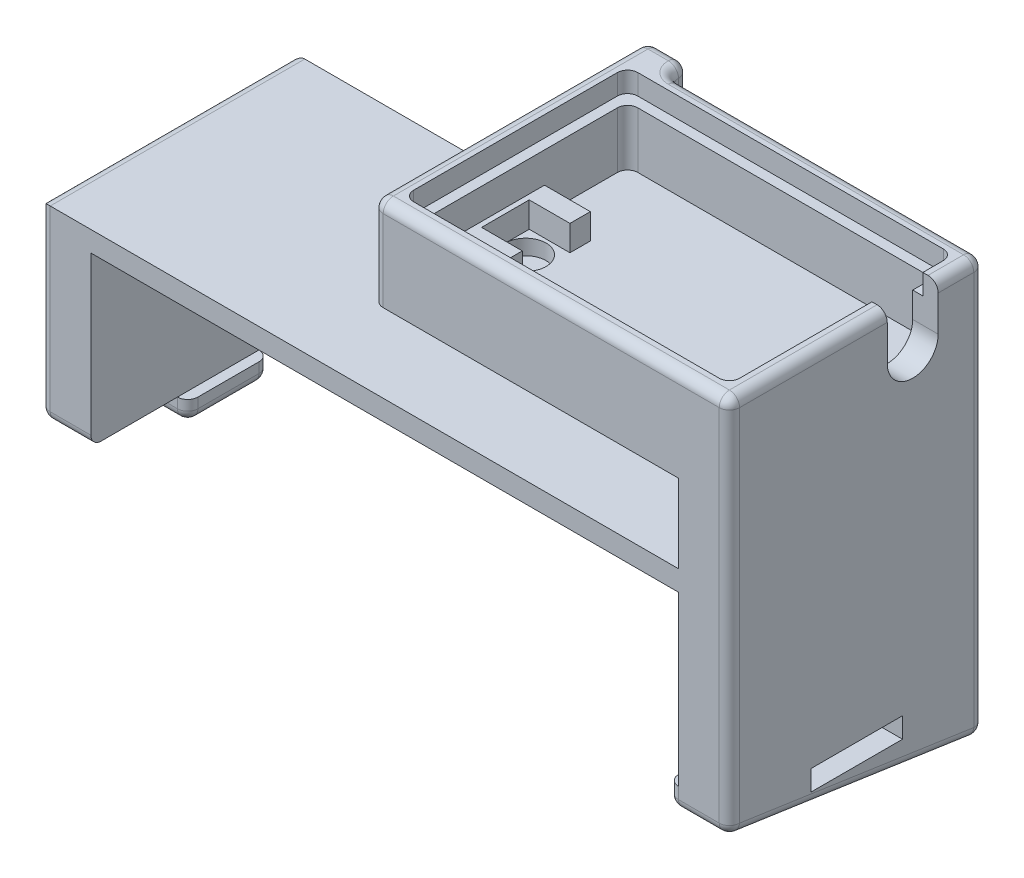
SolidWorks part; units mm, degrees
ref_plane "Front Plane" through (0, 0, 0) normal (0, 0, 1) x (1, 0, 0)
ref_plane "Top Plane" through (0, 0, 0) normal (0, 1, 0) x (1, 0, 0)
ref_plane "Right Plane" through (0, 0, 0) normal (1, 0, 0) x (0, 0, -1)
sketch "Sketch1" plane through (0, 0, 0) normal (0, 0, 1) x (1, 0, 0)
  line L0 (0, 0) -> (30, 0)
  line L1 (30, 0) -> (30, -7.7)
  line L2 (30, -7.7) -> (-32.7, -7.7)
  line L3 (-32.7, -7.7) -> (-32.7, -26.2)
  line L4 (-32.7, -26.2) -> (35, -26.2)
  line L5 (35, -26.2) -> (35, 9)
  line L6 (35, 9) -> (0, 9)
  line L7 (0, 9) -> (0, 0)
  dimension "D1" = 7.7
  dimension "D2" = 30
  dimension "D3" = 35
  dimension "D4" = 67.7
  dimension "D5" = 9
  dimension "D6" = 18.5
extrude "Boss-Extrude1" add sketch "Sketch1" along normal blind 25
sketch "Sketch2" plane through (0, 0, 25) normal (0, 0, 1) x (1, 0, 0)
  line L0 (-32.7, -26.2) -> (35, -26.2) construction
  line L1 (30, -26.2) -> (-27.7, -26.2)
  line L2 (30, -26.2) -> (30, -9.7)
  line L3 (30, -9.7) -> (-27.7, -9.7)
  line L4 (-27.7, -26.2) -> (-27.7, -9.7)
  line L5 (35, -26.2) -> (35, 9) construction
  dimension "D1" = 57.7
  dimension "D2" = 5
  dimension "D3" = 16.5
extrude "Cut-Extrude1" cut sketch "Sketch2" against normal through all
sketch "Sketch3" plane through (0, 9, 0) normal (0, 1, 0) x (1, 0, 0)
  line L0 (35, -25) -> (35, 0) construction
  line L1 (2.5, -2.5) -> (32.5, -2.5)
  line L2 (2.5, -2.5) -> (2.5, -22.5)
  line L3 (2.5, -22.5) -> (32.5, -22.5)
  line L4 (32.5, -2.5) -> (32.5, -22.5)
  line L5 (0, -25) -> (0, 0) construction
  line L6 (35, 0) -> (0, 0) construction
  line L7 (35, -25) -> (0, -25) construction
  dimension "D1" = 2.5
  dimension "D2" = 2.5
  dimension "D3" = 2.5
  dimension "D4" = 2.5
extrude "Cut-Extrude2" cut sketch "Sketch3" against normal blind 7.5
sketch "Sketch4" plane through (0, -26.2, 0) normal (0, -1, 0) x (1, 0, 0)
  line L0 (35, 12.5) -> (35.1733, 12.5) construction
  line L1 (35, 25) -> (35, 0) construction
  line L2 (30, 0) -> (30, 25) construction
  circle A0 centre (30.5, 12.5) radius 2
  dimension "D1" = 4
  dimension "D2" = 0.5
extrude "Cut-Extrude3" cut sketch "Sketch4" against normal up to surface (27.7 mm away) up to face at (17.5, 1.5, 12.5)
sketch "Sketch5" plane through (0, 1.5, 0) normal (0, 1, 0) x (1, 0, 0)
  line L1 (35, 0) -> (0, 0) construction
  line L2 (30, -25) -> (30, -14.4365) construction
  circle A0 centre (5, -15) radius 2
  dimension "D1" = 4
  dimension "D2" = 25
  dimension "D3" = 15
extrude "Cut-Extrude4" cut sketch "Sketch5" against normal up to surface (1.5 mm away) up to face at (19.75, 0, 12.5)
sketch "Sketch6" plane through (0, -26.2, 0) normal (0, -1, 0) x (1, 0, 0)
  line L0 (35, 25) -> (35, 0) construction
  line L1 (35, 25) -> (29, 25)
  line L2 (35, 25) -> (35, 17)
  line L3 (35, 17) -> (29, 17)
  line L4 (29, 25) -> (29, 17)
  line L5 (35, 0) -> (29, 0)
  line L6 (35, 0) -> (35, 8)
  line L7 (35, 8) -> (29, 8)
  line L8 (29, 0) -> (29, 8)
  line L9 (-32.7, 25) -> (-32.7, 0) construction
  line L10 (-32.7, 16.5) -> (-26.7, 16.5)
  line L11 (-32.7, 16.5) -> (-32.7, 8.5)
  line L12 (-32.7, 8.5) -> (-26.7, 8.5)
  line L13 (-26.7, 16.5) -> (-26.7, 8.5)
  line L14 (35, 12.5) -> (36.5966, 12.5) construction
  dimension "D1" = 8
  dimension "D2" = 6
extrude "Boss-Extrude2" add sketch "Sketch6" along normal blind 2
sketch "Sketch7" plane through (0, 0, 0) normal (0, 0, 1) x (1, 0, 0)
  line L0 (0, 9) -> (0, -9.7)
  line L1 (35, 9) -> (0, 9) construction
  line L3 (30, -9.7) -> (-27.7, -9.7) construction
  line L4 (4, -9.7) -> (4, 9)
  line L5 (4, 9) -> (0, 9)
  line L20 (30, -9.7) -> (30, -26.2)
  line L21 (30, -26.2) -> (29, -26.2)
  line L22 (29, -26.2) -> (29, -28.2)
  line L23 (29, -28.2) -> (35, -28.2)
  line L24 (35, -28.2) -> (35, 9)
  line L25 (35, 9) -> (0, 9)
  line L26 (0, 9) -> (0, 0)
  line L27 (0, 0) -> (30, 0)
  line L28 (30, 0) -> (30, -7.7)
  line L29 (30, -7.7) -> (-32.7, -7.7)
  line L30 (-32.7, -7.7) -> (-32.7, -26.2)
  line L31 (-32.7, -26.2) -> (-27.7, -26.2)
  line L32 (-27.7, -26.2) -> (-27.7, -9.7)
  line L33 (-27.7, -9.7) -> (30, -9.7)
  line L47 (0, -9.7) -> (4, -9.7)
  dimension "D2" = 4
  dimension "D1" = 0
sketch "Sketch8" plane through (35, 0, 0) normal (1, 0, 0) x (0, 0, -1)
  line L0 (-25, -28.2) -> (0, -31.86)
  line L1 (0, -31.86) -> (0, -28.2)
  line L3 (-25, -28.2) -> (-25, 9) construction
  line L4 (-25, -28.2) -> (0, -28.2)
  line L5 (0, -28.2) -> (-8, -28.2) construction
  dimension "D1" = 3.66
  dimension "D2" = 8.329
extrude "Boss-Extrude4" add sketch "Sketch8" against normal up to surface (6 mm away) up to face at (29, -27.2, 4)
sketch "Sketch9" plane through (0, 9, 0) normal (0, 1, 0) x (1, 0, 0)
  line L0 (32.5, -22.5) -> (32.5, -2.5) construction
  line L1 (33.5, -23.5) -> (1.5, -23.5)
  line L2 (33.5, -23.5) -> (33.5, -1.5)
  line L3 (33.5, -1.5) -> (1.5, -1.5)
  line L4 (1.5, -23.5) -> (1.5, -1.5)
  line L5 (2.5, -22.5) -> (32.5, -22.5) construction
  line L6 (2.5, -2.5) -> (2.5, -22.5) construction
  line L7 (32.5, -2.5) -> (2.5, -2.5) construction
  dimension "D1" = 1
  dimension "D2" = 1
  dimension "D3" = 1
  dimension "D4" = 1
extrude "Cut-Extrude5" cut sketch "Sketch9" against normal blind 2
fillet "Fillet1" radius 1 8 edges at (33.5, 8, 1.5) (1.5, 8, 1.5) (1.5, 8, 23.5) (33.5, 8, 23.5) (32.5, 4.25, 2.5) (2.5, 4.25, 2.5) (2.5, 4.25, 22.5) (32.5, 4.25, 22.5)
sketch "Sketch10" plane through (-27.7, 0, 0) normal (1, 0, 0) x (0, 0, -1)
  line L0 (-12.5, -9.7) -> (-12.5, -2.753) construction
  line L1 (0, -9.7) -> (-25, -9.7) construction
  circle A0 centre (-14, -12.05) radius 1
  circle A1 centre (-11, -12.05) radius 1
  dimension "D2" = 2
  dimension "D3" = 2
  dimension "D1" = 3
  dimension "D4" = 2.35
extrude "Boss-Extrude5" add sketch "Sketch10" along normal blind 1.5
fillet "Fillet3" radius 1 2 edges at (-26.2, -12.05, 13) (-26.2, -12.05, 10)
extrude "Boss-Extrude6" add sketch "Sketch7" against normal blind 2
fillet "Fillet4" radius 1 34 edges at (-29.7, -28.2, 16.5) (-26.7, -28.2, 12.5) (-29.7, -28.2, 8.5) (-32.7, -28.2, 12.5) (32, -28.2, 25) (35, -30.03, 12.5) (32, -31.86, 0) (29, -30.03, 12.5) (-30.2, -26.2, 0) (-30.2, -26.2, 25) (29, -29.03, 0) (29, -27.2, 25) (-26.7, -27.2, 8.5) (-26.7, -27.2, 16.5) (-32.7, -27.2, 8.5) (-32.7, -27.2, 16.5) (-32.7, -26.2, 4.25) (-32.7, -26.2, 20.75) (-32.7, -16.95, 25) (-32.7, -7.7, 12.5) (-32.7, -16.95, 0) (4, -0.35, -2) (2, -9.7, -2) (2, 9, -2) (0, -0.35, -2) (0, 9, 11.5) (0, 4.5, 25) (17.5, 9, 25) (35, 9, 12.5) (35, -11.43, 0) (35, -9.6, 25)
sketch "Sketch11" plane through (0, 1.5, 0) normal (0, 1, 0) x (1, 0, 0)
  line L0 (2.5, -3.5) -> (2.5, -21.5) construction
  line L1 (7, -19.34) -> (2.5, -19.34)
  line L2 (7, -19.34) -> (7, -17.34)
  line L3 (7, -17.34) -> (2.5, -17.34)
  line L4 (2.5, -19.34) -> (2.5, -17.34)
  line L5 (5, -15) -> (6.4112, -15) construction
  line L6 (7, -12.66) -> (2.5, -12.66)
  line L7 (7, -12.66) -> (7, -10.66)
  line L8 (7, -10.66) -> (2.5, -10.66)
  line L9 (2.5, -12.66) -> (2.5, -10.66)
  dimension "D1" = 2
  dimension "D2" = 2
  dimension "D3" = 4.68
  dimension "D4" = 4.5
extrude "Boss-Extrude7" add sketch "Sketch11" along normal blind 2.5
sketch "Sketch12" plane through (0, 1.5, 0) normal (0, 1, 0) x (1, 0, 0)
  line L0 (7, -17.34) -> (2.5, -17.34) construction
  line L1 (2.5, -12.66) -> (3, -12.66)
  line L2 (2.5, -12.66) -> (2.5, -17.34)
  line L3 (2.5, -17.34) -> (3, -17.34)
  line L4 (3, -12.66) -> (3, -17.34)
  dimension "D1" = 0.5
extrude "Boss-Extrude8" add sketch "Sketch12" along normal blind 2.5
sketch "Sketch13" plane through (35, 0, 0) normal (1, 0, 0) x (0, 0, -1)
  line L0 (-9.5, 9) -> (-9.5, 4.5)
  line L1 (-24, 9) -> (-1, 9) construction
  line L2 (-4.5, 4.5) -> (-4.5, 9)
  line L3 (-4.5, 9) -> (-9.5, 9)
  line L4 (0, 0) -> (0, 8) construction
  arc A0 (-9.5, 4.5) -> (-4.5, 4.5) centre (-7, 4.5) ccw
  dimension "D1" = 2.5
  dimension "D2" = 4.5
  dimension "D3" = 7
extrude "Cut-Extrude6" cut sketch "Sketch13" against normal up to surface (2.5 mm away) up to face at (32.5, 3.7, 12.5)
